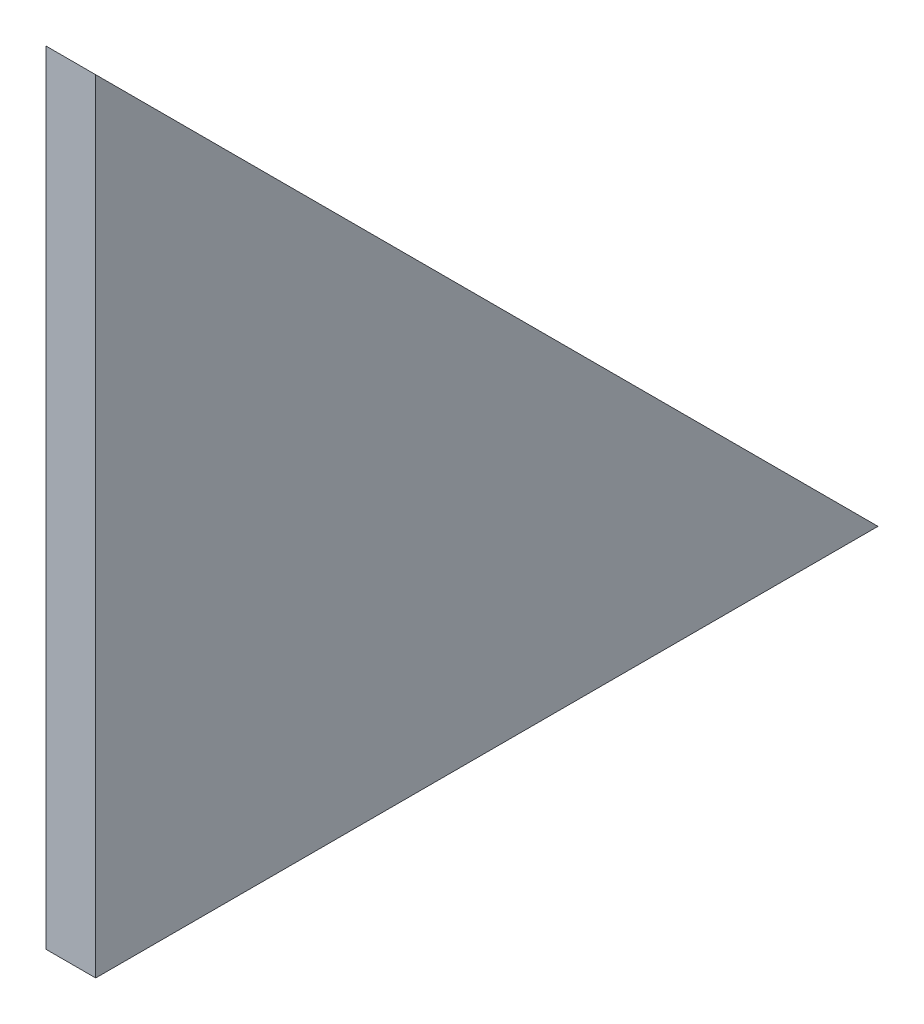
SolidWorks part; units mm, degrees
material "Acero al carbono no aleado"
ref_plane "Alzado" through (0, 0, 0) normal (0, 0, 1) x (1, 0, 0)
ref_plane "Planta" through (0, 0, 0) normal (0, 1, 0) x (1, 0, 0)
ref_plane "Vista lateral" through (0, 0, 0) normal (1, 0, 0) x (0, 0, -1)
sketch "Croquis1" plane through (0, 0, 0) normal (0, 0, 1) x (1, 0, 0)
  line L1 (3.175, -50) -> (-3.175, -50)
  line L2 (3.175, -50) -> (3.175, 50)
  line L3 (3.175, 50) -> (-3.175, 50)
  line L4 (-3.175, -50) -> (-3.175, 50)
  line L5 (3.175, -50) -> (-3.175, 50) construction
  line L6 (3.175, 50) -> (-3.175, -50) construction
  line L8 (3.175, -50) -> (3.175, -47)
  point P0 (0, 0)
  point P6 (0, 0)
  point P8 (0, 0)
  dimension "D1" = 100
  dimension "D3" = 6.35
extrude "Saliente-Extruir1" add sketch "Croquis1" along normal mid plane 100 contours L4 L1 L2 L3
sketch "Croquis2" plane through (3.175, 0, 0) normal (1, 0, 0) x (0, 0, -1)
  line L0 (-50, 50) -> (50, -50)
  line L4 (-50, 50) -> (-50, -50)
  line L5 (-50, -50) -> (50, -50)
  line L6 (50, -50) -> (50, 50)
  line L7 (50, 50) -> (-50, 50)
  line L8 (-50, 50) -> (-50, -50)
  line L10 (50, -50) -> (50, 50)
  line L11 (50, 50) -> (-50, 50)
  line L13 (-50, -50) -> (50, -50)
  line M7 (50, -50) -> (50, 50)
  line M8 (50, 50) -> (-50, 50)
  dimension "D1" = 0
extrude "Cortar-Extruir1" cut sketch "Croquis2" against normal blind 100 contours L0 M8 M7 region at (3.175, 16.6667, -16.6667)
